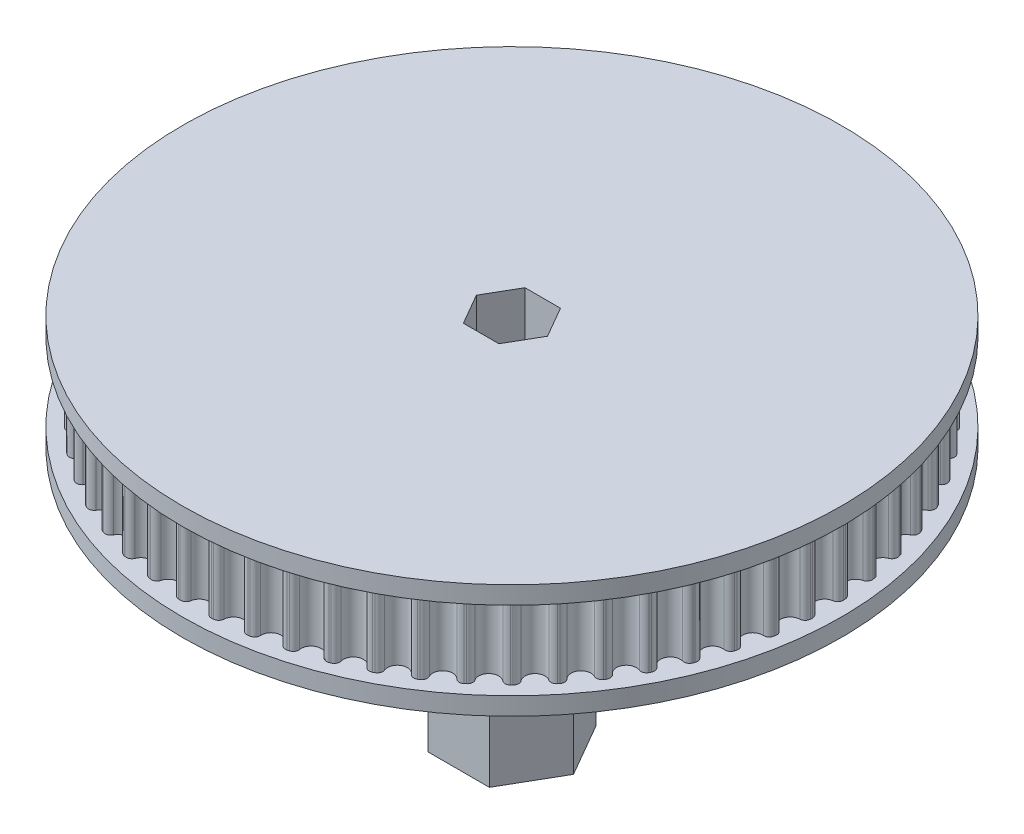
SolidWorks part; units mm, degrees
ref_plane "Front Plane" through (0, 0, 0) normal (0, 0, 1) x (1, 0, 0)
ref_plane "Top Plane" through (0, 0, 0) normal (0, 1, 0) x (1, 0, 0)
ref_plane "Right Plane" through (0, 0, 0) normal (1, 0, 0) x (0, 0, -1)
sketch "Sketch1" plane through (0, 0, 0) normal (0, 1, 0) x (1, 0, 0)
  line L0 (0, 0) -> (0, 28.2667) construction
  line L1 (0, 0) -> (2.9202, 27.7837) construction
  circle A0 centre (0, 0) radius 28.2667 construction
  circle A1 centre (0, 0) radius 27.0467 construction
  circle A2 centre (0, 27.9367) radius 0.89 construction
  circle A5 centre (2.9202, 27.7837) radius 0.89 construction
  arc A6 (0, 27.0467) -> (0.8804, 27.8061) centre (0, 27.9367) ccw
  arc A7 (0.8804, 27.8061) -> (1.3997, 28.2321) centre (1.3749, 27.7327) cw
  arc A8 (1.559, 28.2237) -> (2.031, 27.7458) centre (1.5314, 27.7245) cw
  arc A9 (2.8272, 26.8986) -> (2.031, 27.7458) centre (2.9202, 27.7837) cw
  arc A10 (1.3997, 28.2321) -> (1.559, 28.2237) centre (0, 0) cw
  arc A11 (0, 27.0467) -> (2.8272, 26.8986) centre (0, 0) ccw
  dimension "D1" = 56.5335
  dimension "D3" = 1.78
  dimension "D4" = 0.5
  dimension "D2" = 1.22
  dimension "D5" = 6
extrude "Boss-Extrude1" add sketch "Sketch1" along normal mid plane 7 contours A6 A11 A9 A8 A7 region at (0.001, 0, -0.0192)
ref_axis "Axis1" through (0, 3.3, 0) along (0, -1, 0)
pattern_circular "CirPattern1" count 60 over 360 about axis through (0, 3.3, 0) along (0, -1, 0) of "Boss-Extrude1"
sketch "Sketch2" plane through (0, 0, 0) normal (1, 0, 0) x (0, 0, -1)
  line L10 (0, 3.5) -> (29.4415, 3.5) construction
  line L11 (0, 3.5) -> (0, 5.0875) construction
  line L12 (0, 5.0875) -> (29.4415, 5.0875) construction
  line L15 (29.4415, 3.5) -> (29.4415, 5.0875) construction
  line L20 (0, 3.3) -> (0, -3.3) construction
  line L22 (29.4415, 5.0875) -> (0, 5.0875)
  line L23 (29.4415, 5.0875) -> (29.4415, 3.5)
  line L24 (29.4415, 3.5) -> (0, 3.5)
  line L25 (0, 5.0875) -> (0, 3.5)
  dimension "D1" = 1.5875
  dimension "D2" = 29.4415
  dimension "D3" = 3.5
revolve "Revolve3" add sketch "Sketch2" angle 360 about axis through (0, 3.3, 0) along (0, -1, 0) region at (0, 4.2937, -14.7207)
mirror "Mirror1" about plane through (0, 0, 0) normal (0, 1, 0) of "Revolve3"
sketch "Sketch3" plane through (0, 0, 0) normal (0, -1, 0) x (-1, 0, 0)
  circle A0 centre (0, 0) radius 22.2977
  dimension "D1" = 44.5955
extrude "Cut-Extrude1" cut sketch "Sketch3" against normal through all both and the other way through all
ref_plane "Plane1" through (0, 0, 0) normal (0.9548, 0, 0.2973) x (0, -1, 0)
sketch "Sketch4" plane through (0, 0, 0) normal (0, 0, 1) x (1, 0, 0)
  line L0 (12.5, -7.945) -> (12.5, -14.945)
  line L1 (-12.5, -14.945) -> (-12.5, -7.945)
  line L2 (-12.5, -14.945) -> (-12.5, -7.945)
  line L3 (12.5, -7.945) -> (12.5, -14.945)
  line L4 (-18.5, -7.945) -> (-12.5, -7.945)
  line L5 (12.5, -7.945) -> (18.5, -7.945)
  line L6 (12.5, -7.945) -> (18.5, -7.945)
  line L7 (-18.5, -7.945) -> (-12.5, -7.945)
  line L8 (12.5, -7.945) -> (13.77, -7.945)
  line L9 (16.6275, -5.0875) -> (22.2977, -5.0875)
  line L11 (-22.2977, -5.0875) -> (22.2977, -5.0875) construction
  line L12 (-29.4415, -5.0875) -> (29.4415, -5.0875) construction
  line L13 (22.2977, -5.0875) -> (22.2977, 5.0875)
  line L14 (22.2977, 5.0875) -> (-22.2977, 5.0875) construction
  line L16 (22.2977, 5.0875) -> (0, 5.0875)
  line L17 (0, 5.0875) -> (0, -27.645)
  line L18 (0, -27.645) -> (12.5, -27.645)
  line L19 (12.5, -27.645) -> (12.5, -14.945)
  line L21 (22.2977, 5.0875) -> (-22.2977, 5.0875)
  line L22 (-18.5, -14.945) -> (18.5, -14.945) construction
  arc A0 (13.77, -7.945) -> (16.6275, -5.0875) centre (16.6275, -7.945) cw
  dimension "D1" = 1.27
  dimension "D2" = 12.7
revolve "Revolve4" add sketch "Sketch4" angle 360 about L17 region at (8.4878, -9.0396, 0)
sketch "Sketch5" plane through (0, -27.645, 0) normal (0, -1, 0) x (1, 0, 0)
  line L1 (2.7496, -4.7625) -> (5.4993, 0)
  line L2 (5.4993, 0) -> (2.7496, 4.7625)
  line L3 (2.7496, 4.7625) -> (-2.7496, 4.7625)
  line L4 (-2.7496, 4.7625) -> (-5.4993, 0)
  line L5 (-5.4993, 0) -> (-2.7496, -4.7625)
  line L6 (-2.7496, -4.7625) -> (2.7496, -4.7625)
  circle A0 centre (0, 0) radius 4.7625 construction
  circle A4 centre (0, 0) radius 12.5 construction
  circle A5 centre (0, 0) radius 12.5
  dimension "D1" = 9.525
extrude "Cut-Extrude2" cut sketch "Sketch5" against normal up to surface (12.7 mm away)
sketch "Sketch6" plane through (0, 5.0875, 0) normal (0, 1, 0) x (1, 0, 0)
  line L1 (-1.5877, 2.75) -> (-3.1754, 0)
  line L2 (-3.1754, 0) -> (-1.5877, -2.75)
  line L3 (-1.5877, -2.75) -> (1.5877, -2.75)
  line L4 (1.5877, -2.75) -> (3.1754, 0)
  line L5 (3.1754, 0) -> (1.5877, 2.75)
  line L6 (1.5877, 2.75) -> (-1.5877, 2.75)
  circle A0 centre (0, 0) radius 2.75 construction
  dimension "D1" = 5.5
extrude "Cut-Extrude3" cut sketch "Sketch6" against normal offset from surface (30.1925 mm away) 2.54 up to face at (0, -27.645, 0)
sketch "Sketch7" plane through (0, -27.645, 0) normal (0, -1, 0) x (1, 0, 0)
  circle A0 centre (0, 0) radius 1.6 construction
  circle A1 centre (0, 0) radius 1.6
extrude "Cut-Extrude4" cut sketch "Sketch7" against normal through all both and the other way through all
equation "\"TEETH_NUM\"= 60"
equation "\"TOOTH_PITCH\"= 3mm"
equation "\"PITCH_LINE_OFFSET\"= .015in"
equation "\"DIAMETER_PER_GROOVE\"= \"OUTSIDE_DIAMETER\" / \"TEETH_NUM\" * 1in"
equation "\"PITCH_DIAMETER\"= ( ( \"TEETH_NUM\" * 3 - 1.31 ) / 3.1415 + .415 ) * 1mm"
equation "\"OUTSIDE_DIAMETER\"= \"PITCH_DIAMETER\" - \"PITCH_LINE_OFFSET\" * 2"
equation "\"D1@Sketch1\"=\"OUTSIDE_DIAMETER\""
equation "\"TOOTH_HEIGHT\"= 1.22mm"
equation "\"D2@Sketch1\"=\"TOOTH_HEIGHT\""
equation "\"TOOTH_DIAMETER\"= 1.78mm"
equation "\"INTERNAL_RADIUS\"= .5mm"
equation "\"D3@Sketch1\"=\"TOOTH_DIAMETER\""
equation "\"D5@Sketch1\"=360 / \"TEETH_NUM\""
equation "\"D4@Sketch1\"=\"INTERNAL_RADIUS\""
equation "\"D1@CirPattern1\"=\"TEETH_NUM\""
equation "\"BELT_GAP\"= 7mm"
equation "\"D2@Sketch2\"=\"PITCH_DIAMETER\"/2+1/32"
equation "\"D3@Sketch2\"=\"BELT_GAP\"/2"
equation "\"D1@Sketch3\"=\"PITCH_DIAMETER\"-.5"
equation "\"D1@Boss-Extrude1\"=\"BELT_GAP\""
